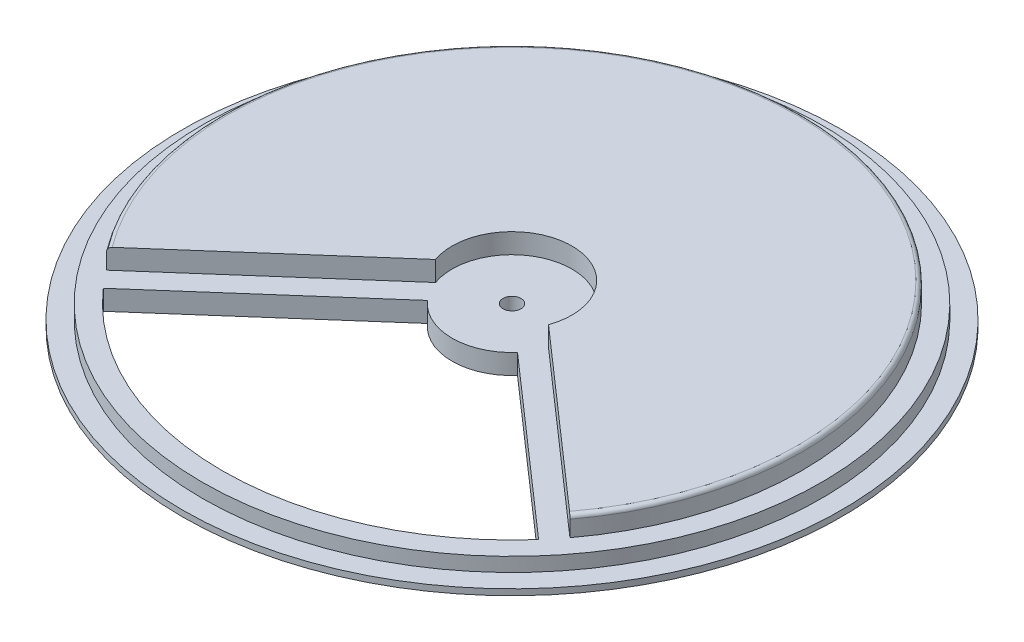
SolidWorks part; units mm, degrees
material "1060 Alloy"
ref_plane "Front Plane" through (0, 0, 0) normal (0, 0, 1) x (1, 0, 0)
ref_plane "Top Plane" through (0, 0, 0) normal (0, 1, 0) x (1, 0, 0)
ref_plane "Right Plane" through (0, 0, 0) normal (1, 0, 0) x (0, 0, -1)
sketch "Sketch1" plane through (0, 0, 0) normal (0, 1, 0) x (1, 0, 0)
  circle A0 centre (0, 0) radius 209.55
  dimension "D1" = 419.1
extrude "Boss-Extrude1" add sketch "Sketch1" along normal blind 3.81
sketch "Sketch2" plane through (0, 3.81, 0) normal (0, 1, 0) x (1, 0, 0)
  circle A0 centre (0, 0) radius 196.85
  dimension "D1" = 393.7
extrude "Boss-Extrude2" add sketch "Sketch2" along normal blind 8.89
sketch "Sketch3" plane through (0, 12.7, 0) normal (0, 1, 0) x (1, 0, 0)
  circle A0 centre (0, 0) radius 5.715
  dimension "D1" = 11.43
extrude "Cut-Extrude1" cut sketch "Sketch3" against normal through all
sketch "Sketch4" plane through (0, 12.7, 0) normal (0, 1, 0) x (1, 0, 0)
  line L0 (-147.32, -110.49) -> (-35.921, -12.7)
  line L1 (147.32, -110.49) -> (35.921, -12.7)
  line L2 (-138.3923, -121.4857) -> (-28.6329, -25.135)
  line L3 (28.6329, -25.135) -> (138.3923, -121.4857)
  line L4 (0, 0) -> (-50000, 0) construction
  arc A0 (-138.3923, -121.4857) -> (138.3923, -121.4857) centre (0, 0) ccw
  arc A1 (35.921, -12.7) -> (-35.921, -12.7) centre (0, 0) ccw
  arc A2 (147.32, -110.49) -> (-147.32, -110.49) centre (0, 0) ccw
  arc A3 (-28.6329, -25.135) -> (28.6329, -25.135) centre (0, 0) ccw
  dimension "D1" = 368.3
  dimension "D2" = 76.2
  dimension "D3" = 110.49
  dimension "D5" = 12.7
extrude "Boss-Extrude3" add sketch "Sketch4" along normal blind 12.7 contours L1 A1 L0 A2
extrude "Cut-Extrude2" cut sketch "Sketch4<3>" against normal through all
sketch "Sketch4<3>" plane through (0, 12.7, 0) normal (0, 1, 0) x (1, 0, 0) same geometry as "Sketch4"
fillet "Fillet1" radius 2.54 1 edges at (0, 25.4, -184.15)
